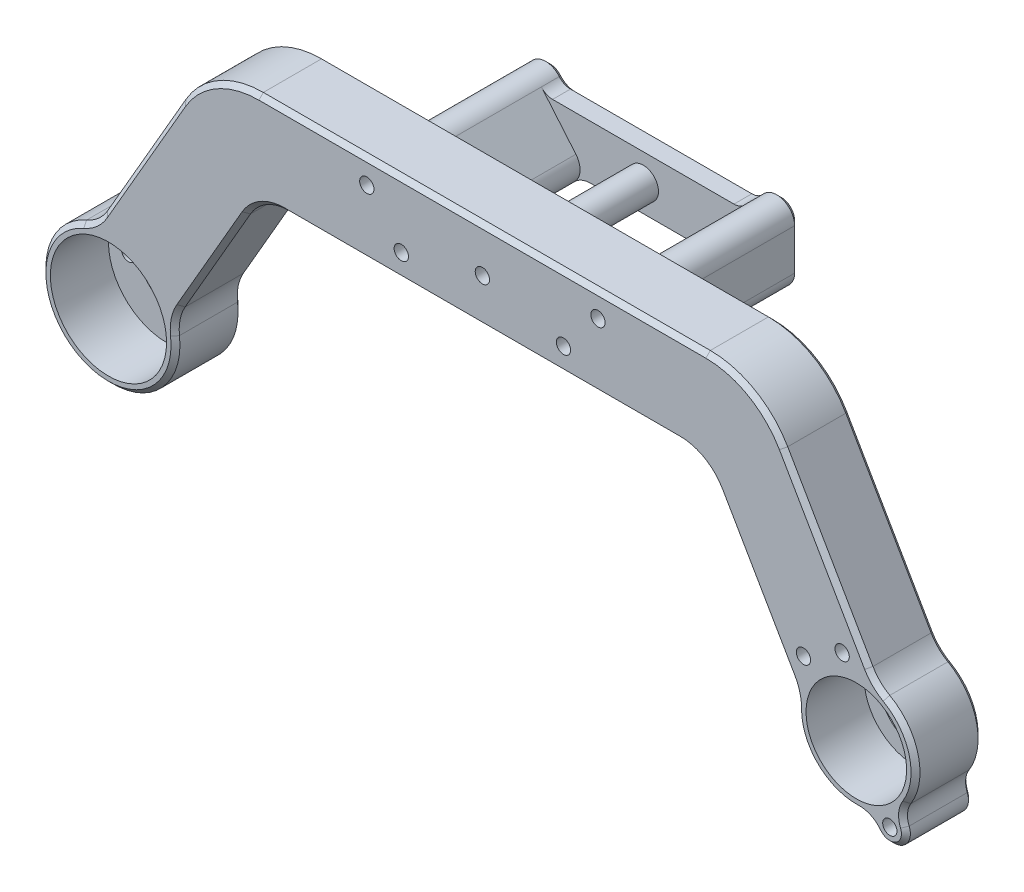
SolidWorks part; units mm, degrees
other "Markup1"
sketch "Sketch2"
ref_plane "Front Plane" through (0, 0, 0) normal (0, 0, 1) x (1, 0, 0)
ref_plane "Top Plane" through (0, 0, 0) normal (0, 1, 0) x (1, 0, 0)
ref_plane "Right Plane" through (0, 0, 0) normal (1, 0, 0) x (0, 0, -1)
ref_axis "X" through (-88.99, 0, 0) along (1, 0, 0)
ref_axis "Y" through (0, 55, 0) along (0, -1, 0)
ref_axis "Z" through (0, 0, -88.99) along (0, 0, 1)
sketch "Sketch1" plane through (0, 0, 0) normal (0, 0, 1) x (1, 0, 0)
  line L0 (0, 10) -> (0, -10) construction
  line L1 (-50, 10) -> (50, 10)
  line L2 (-50, -10) -> (50, -10)
  line L3 (67.3205, 0) -> (92.3205, -43.3013)
  line L4 (75, -53.3013) -> (50, -10)
  line L5 (-75, -53.3013) -> (-50, -10)
  line L6 (-67.3205, 0) -> (-92.3205, -43.3013)
  arc A0 (50, 10) -> (67.3205, 0) centre (50, -10) cw
  arc A1 (92.3205, -43.3013) -> (75, -53.3013) centre (83.6603, -48.3013) cw
  arc A3 (-92.3205, -43.3013) -> (-75, -53.3013) centre (-83.6603, -48.3013) ccw
  arc A4 (-50, 10) -> (-67.3205, 0) centre (-50, -10) ccw
  point P4 (0, 0)
  dimension "D1" = 20
  dimension "D2" = 50
  dimension "D3" = 60
  dimension "D4" = 50
extrude "Boss-Extrude1" add sketch "Sketch1" along normal mid plane 15
ref_plane "Plane1" through (0, 0, 28.5) normal (0, 0, 1) x (1, 0, 0)
sketch "Sketch3" plane through (0, 0, 0) normal (0, 0, 1) x (1, 0, 0)
  line L0 (-22, 0) -> (22, 0) construction
  line L1 (25.8567, 4.5963) -> (18.1433, -4.5963) construction
  line L2 (0, 0) -> (0, 1.6) construction
  line L3 (-25.8567, 4.5963) -> (-18.1433, -4.5963) construction
  circle A1 centre (0, 0) radius 1.6
  circle A2 centre (25.8567, 4.5963) radius 1.6
  circle A3 centre (18.1433, -4.5963) radius 1.6
  circle A4 centre (-25.8567, 4.5963) radius 1.6
  circle A5 centre (-18.1433, -4.5963) radius 1.6
  point P7 (0, 0)
  point P10 (22, 0)
  dimension "D6" = 3.2
  dimension "D3" = 12
  dimension "D4" = 22
  dimension "D5" = 50
extrude "Cut-Extrude1" cut sketch "Sketch3" against normal through all both and the other way through all
sketch "Sketch4" plane through (0, 0, 28.5) normal (0, 0, 1) x (1, 0, 0)
  line L0 (25.8567, 4.5963) -> (18.1433, -4.5963) construction
  line L1 (-25.8567, 4.5963) -> (-18.1433, -4.5963) construction
  line L2 (25.8567, 4.5963) -> (18.1433, -4.5963) construction
  line L3 (-25.8567, 4.5963) -> (-18.1433, -4.5963) construction
  line L4 (15.0791, -2.0251) -> (22.7925, 7.1674)
  line L5 (29.8567, 4.5963) -> (29.8567, -4.5963)
  line L6 (25.8567, -8.5963) -> (18.1433, -8.5963)
  line L7 (0, 0) -> (0, 1.6) construction
  line L8 (0, 0) -> (0, 1.6) construction
  line L9 (-25.8567, -8.5963) -> (-18.1433, -8.5963)
  line L10 (-29.8567, 4.5963) -> (-29.8567, -4.5963)
  line L11 (-15.0791, -2.0251) -> (-22.7925, 7.1674)
  line L12 (20.289, 6) -> (-20.289, 6)
  line L13 (0, 6) -> (0, 3.4)
  line L14 (0, -3.4) -> (0, -6)
  line L15 (-11.8193, -6) -> (11.8193, -6)
  circle A0 centre (25.8567, 4.5963) radius 1.6 construction
  circle A1 centre (18.1433, -4.5963) radius 1.6 construction
  circle A2 centre (-25.8567, 4.5963) radius 1.6 construction
  circle A3 centre (-18.1433, -4.5963) radius 1.6 construction
  circle A4 centre (0, 0) radius 1.6 construction
  circle A5 centre (25.8567, 4.5963) radius 1.6
  circle A6 centre (18.1433, -4.5963) radius 1.6
  circle A7 centre (-25.8567, 4.5963) radius 1.6
  circle A8 centre (-18.1433, -4.5963) radius 1.6
  circle A9 centre (0, 0) radius 1.6
  arc A10 (22.7925, 7.1674) -> (29.8567, 4.5963) centre (25.8567, 4.5963) cw
  arc A11 (29.8567, -4.5963) -> (25.8567, -8.5963) centre (25.8567, -4.5963) cw
  arc A12 (18.1433, -8.5963) -> (15.0791, -2.0251) centre (18.1433, -4.5963) cw
  arc A13 (-29.8567, -4.5963) -> (-25.8567, -8.5963) centre (-25.8567, -4.5963) ccw
  arc A14 (-22.7925, 7.1674) -> (-29.8567, 4.5963) centre (-25.8567, 4.5963) ccw
  arc A15 (-18.1433, -8.5963) -> (-15.0791, -2.0251) centre (-18.1433, -4.5963) ccw
  circle A16 centre (0, 0) radius 3.4
  arc A17 (22.7925, 7.1674) -> (20.289, 6) centre (20.289, 9.2681) cw
  arc A18 (11.8193, -6) -> (15.3326, -7.4424) centre (11.8193, -11) cw
  arc A19 (-11.8193, -6) -> (-15.3326, -7.4424) centre (-11.8193, -11) ccw
  arc A20 (-22.7925, 7.1674) -> (-20.289, 6) centre (-20.289, 9.2681) ccw
  dimension "D1" = 4
  dimension "D4" = 4
  dimension "D5" = 6.8
  dimension "D6" = 12
  dimension "D7" = 5
  dimension "D2" = 4
  dimension "D3" = 4
extrude "Boss-Extrude2" add sketch "Sketch4" against normal up to surface (21 mm away) separate body contours L9 A15 L11 A14 L10 A13 A8 A7 | A12 L6 A11 L5 A10 L4 A6 A5 | A16 A9 region at (23.3022, -1.3358, 28.5) region at (2.3362, 2.3362, 28.5) region at (-23.3022, -1.3358, 28.5) up to face at (-19.7433, -4.5963, 7.5)
extrude "Boss-Extrude3" add sketch "Sketch4<3>" along normal blind 5 contours L9 A15 L11 A14 L10 A13 A8 A7 | A20 L11 A15 A19 L15 L14 A16 L13 L12 | A16 A9 | L15 A18 A12 L4 A17 L12 L13 A16 L14 | A12 L6 A11 L5 A10 L4 A6 A5 region at (9.4772, 0.5266, 28.5) region at (23.3022, -1.3358, 28.5) region at (-9.4772, 0.5266, 28.5) region at (2.3362, 2.3362, 28.5) region at (-23.3022, -1.3358, 28.5)
sketch "Sketch4<3>" plane through (0, 0, 28.5) normal (0, 0, 1) x (1, 0, 0) same geometry as "Sketch4"
chamfer "Chamfer1" distance 1 angle 45 16 edges at (22, -8.5963, 33.5) (28.6852, -7.4247, 33.5) (16.6241, -8.2966, 33.5) (29.8567, 0, 33.5) (13.7183, -6.3746, 33.5) (27.2248, 8.355, 33.5) (0, -6, 33.5) (21.6702, 6.3062, 33.5) (-13.7183, -6.3746, 33.5) (0, 6, 33.5) (-16.6241, -8.2966, 33.5) (-21.6702, 6.3062, 33.5) (-22, -8.5963, 33.5) (-27.2248, 8.355, 33.5) (-28.6852, -7.4247, 33.5) (-29.8567, 0, 33.5)
sketch "Sketch5" plane through (0, 0, 0) normal (0, 0, 1) x (1, 0, 0)
  line L0 (-92.1603, -48.3013) -> (-75.1603, -48.3013) construction
  circle A1 centre (83.6603, -48.3013) radius 13.25
  circle A3 centre (83.6603, -48.3013) radius 11.25
  circle A4 centre (83.6603, -48.3013) radius 7.5
  circle A5 centre (-83.6603, -48.3013) radius 13
  circle A6 centre (-83.6603, -48.3013) radius 15
  circle A7 centre (-83.6603, -48.3013) radius 5.5
  circle A8 centre (-75.1603, -48.3013) radius 1.6
  circle A9 centre (-92.1603, -48.3013) radius 1.6
  point P14 (-83.6603, -48.3013)
  dimension "D1" = 2
  dimension "D2" = 22.5
  dimension "D3" = 15
  dimension "D4" = 26
  dimension "D6" = 11
  dimension "D8" = 3.2
  dimension "D7" = 17
  dimension "D5" = 2
extrude "Boss-Extrude4" add sketch "Sketch5" along normal up to surface and the other way up to surface contours A1 A3 region at (70.785, -48.3013, 0) up to face at (-19.7433, -4.5963, 7.5) other way up to face at (-19.7433, -4.5963, -7.5)
extrude "Cut-Extrude2" cut sketch "Sketch5<3>" against normal through all both and the other way through all contours A3
sketch "Sketch5<3>" plane through (0, 0, 0) normal (0, 0, 1) x (1, 0, 0) same geometry as "Sketch5"
extrude "Boss-Extrude5" add sketch "Sketch5<4>" against normal blind 2 from surface contours A3 A4 region at (72.7285, -48.3013, 0) starting at face at (72.4103, -48.3013, 7.5)
sketch "Sketch5<4>" plane through (0, 0, 0) normal (0, 0, 1) x (1, 0, 0) same geometry as "Sketch5"
extrude "Cut-Extrude3" cut sketch "Sketch5<5>" against normal through all both and the other way through all contours A5
sketch "Sketch5<5>" plane through (0, 0, 0) normal (0, 0, 1) x (1, 0, 0) same geometry as "Sketch5"
extrude "Boss-Extrude6" add sketch "Sketch5<6>" along normal up to surface (7.5 mm away) and the other way up to surface (7.5 mm away) contours A6 A5 region at (-98.236, -48.3013, 0) up to face at (1.2932, -17.4059, 7.5) other way up to face at (1.2932, -17.4059, -7.5)
sketch "Sketch5<6>" plane through (0, 0, 0) normal (0, 0, 1) x (1, 0, 0) same geometry as "Sketch5"
extrude "Boss-Extrude7" add sketch "Sketch5<7>" against normal blind 2 from surface contours A5 A9 A7 A8 region at (-96.2926, -48.3013, 0) starting at face at (0.0369, -19.5819, 7.5)
sketch "Sketch5<7>" plane through (0, 0, 0) normal (0, 0, 1) x (1, 0, 0) same geometry as "Sketch5"
fillet "Fillet1" radius 10 6 edges at (87.9742, -35.7732, 0) (70.6537, -45.7732, 0) (-86.7303, -33.6188, 0) (-69.4098, -43.6188, 0) (50, -10, 0) (-50, -10, 0)
sketch "Sketch6" plane through (0, 0, 0) normal (0, 0, 1) x (1, 0, 0)
  line L0 (71.8301, -37.8109) -> (80.4904, -32.8109) construction
  line L1 (76.1603, -35.3109) -> (83.6603, -48.3013) construction
  line L2 (83.6603, -48.3013) -> (91.1603, -61.2917) construction
  line L3 (75, -53.3013) -> (50, -10) construction
  circle A0 centre (91.1603, -61.2917) radius 1.6
  circle A1 centre (80.4904, -32.8109) radius 1.6
  circle A2 centre (71.8301, -37.8109) radius 1.6
  arc A3 (88.3078, -63.488) -> (94.4885, -59.9195) centre (91.1603, -61.2917) ccw
  arc A4 (94.4885, -59.9195) -> (94.878, -55.3529) centre (99.1111, -58.0138) cw
  circle A5 centre (83.6603, -48.3013) radius 13.25 construction
  arc A6 (88.3078, -63.488) -> (84.1582, -61.5419) centre (84.3462, -66.5384) ccw
  arc A7 (84.1582, -61.5419) -> (94.878, -55.3529) centre (83.6603, -48.3013) ccw
  dimension "D4" = 3.2
  dimension "D5" = 2
  dimension "D6" = 5
  dimension "D1" = 10
  dimension "D2" = 15
  dimension "D3" = 15
extrude "Boss-Extrude8" add sketch "Sketch6" along normal up to surface (7.5 mm away) and the other way up to surface (7.5 mm away) contours A7 A6 A3 A4 A0 region at (86.5301, -61.8816, 0) up to face at (0.2077, -23.3873, 7.5) other way up to face at (0.2077, -23.3873, -7.5)
extrude "Cut-Extrude4" cut sketch "Sketch6<3>" against normal through all both and the other way through all contours A2 | A1 | A0 region at (91.1603, -61.2917, 0) region at (80.4904, -32.8109, 0) region at (71.8301, -37.8109, 0)
sketch "Sketch6<3>" plane through (0, 0, 0) normal (0, 0, 1) x (1, 0, 0) same geometry as "Sketch6"
sketch "Sketch7" plane through (0, 0, 0) normal (0, 0, 1) x (1, 0, 0)
  circle A0 centre (80.4904, -32.8109) radius 3
  circle A1 centre (71.8301, -37.8109) radius 3
  circle A2 centre (91.1603, -61.2917) radius 3
  dimension "D1" = 6
extrude "Cut-Extrude5" cut sketch "Sketch7" against normal blind 3.5 from surface starting at face at (70.2301, -37.8109, 7.5)
chamfer "Chamfer2" distance 1 angle 45 38 edges at (0, -10, -7.5) (49.2265, -11.3397, -7.5) (-49.2265, -11.3397, -7.5) (60.9794, -29.0169, -7.5) (-60.1934, -27.6554, -7.5) (70.0858, -45.5012, -7.5) (-68.6367, -43.3061, -7.5) (-91.1603, -61.2917, -7.5) (88.0225, -35.1454, -7.5) (-86.8461, -32.7929, -7.5) (76.8565, -16.5169, -7.5) (-76.0705, -15.1554, -7.5) (60, 7.3205, -7.5) (-60, 7.3205, -7.5) (0, 10, -7.5) (0, -10, 7.5) (49.2265, -11.3397, 7.5) (-49.2265, -11.3397, 7.5) (60.9794, -29.0169, 7.5) (-60.1934, -27.6554, 7.5) (70.0858, -45.5012, 7.5) (-68.6367, -43.3061, 7.5) (-91.1603, -61.2917, 7.5) (88.0225, -35.1454, 7.5) (-86.8461, -32.7929, 7.5) (76.8565, -16.5169, 7.5) (-76.0705, -15.1554, 7.5) (60, 7.3205, 7.5) (-60, 7.3205, 7.5) (0, 10, 7.5) (86.4692, -62.0115, -7.5) (92.9603, -64.4093, -7.5) (94.1292, -57.5889, -7.5) (96.5024, -45.0391, -7.5) (74.4141, -57.7918, 7.5) (86.4692, -62.0115, 7.5) (92.9603, -64.4093, 7.5) (94.1292, -57.5889, 7.5)
mirror "Mirror1" about plane through (0, 0, 0) normal (0, 0, 1) of bodies 115 106
delete or keep bodies "Body-Delete/Keep 1" type keep bodies bodies 117 116
